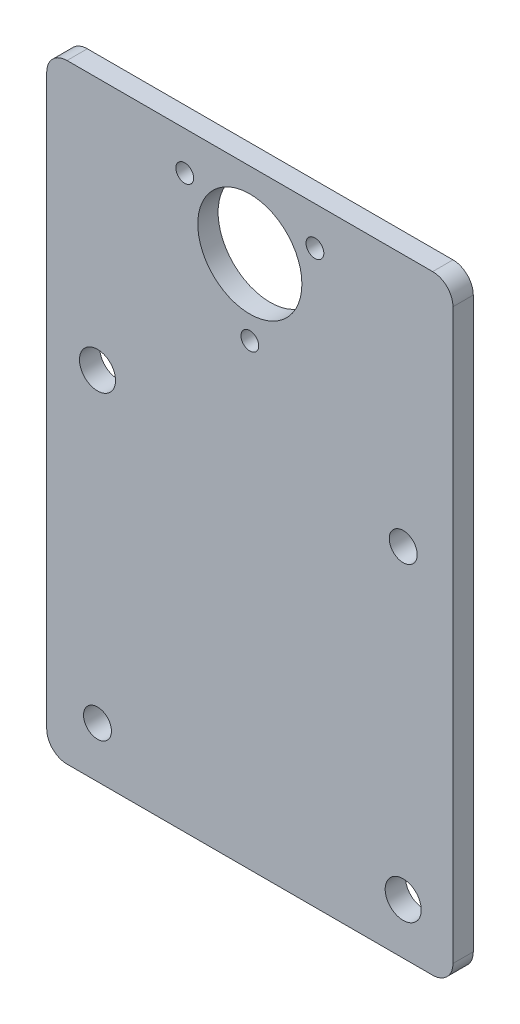
SolidWorks part; units mm, degrees
ref_plane "Płaszczyzna przednia" through (0, 0, 0) normal (0, 0, 1) x (1, 0, 0)
ref_plane "Płaszczyzna górna" through (0, 0, 0) normal (0, 1, 0) x (1, 0, 0)
ref_plane "Płaszczyzna prawa" through (0, 0, 0) normal (1, 0, 0) x (0, 0, -1)
sketch "Szkic1" plane through (0, 0, 0) normal (0, 0, 1) x (1, 0, 0)
  line L1 (-37.347, -20.7576) -> (42.653, -20.7576)
  line L2 (-37.347, -20.7576) -> (-37.347, 99.2424)
  line L3 (-37.347, 99.2424) -> (42.653, 99.2424)
  line L4 (42.653, -20.7576) -> (42.653, 99.2424)
  circle A0 centre (-27.347, 49.4424) radius 3.55
  circle A1 centre (-27.347, -10.7576) radius 2.75
  circle A2 centre (32.853, -10.7576) radius 3.55
  circle A3 centre (32.853, 49.4424) radius 2.75
  circle A4 centre (2.653, 84.2424) radius 10.25
  circle A5 centre (-10.1642, 91.6424) radius 1.75
  circle A6 centre (15.4702, 91.6424) radius 1.75
  circle A7 centre (2.653, 69.4424) radius 1.75
  point P21 (0, 0)
  point P24 (0, 0)
  dimension "D1" = 60.2
  dimension "D2" = 60.2
  dimension "D11" = 5.5
  dimension "D12" = 5.5
  dimension "D13" = 7.1
  dimension "D14" = 7.1
  dimension "D15" = 3.5
  dimension "D16" = 3.5
  dimension "D17" = 20.5
  dimension "3,5" = 3.5
  dimension "D18" = 14.8
  dimension "D19" = 14.8
  dimension "D20" = 14.8
  dimension "D3" = 60.2
  dimension "D4" = 60.2
  dimension "D5" = 10
  dimension "D6" = 10
  dimension "D7" = 10
  dimension "D8" = 10
  dimension "D9" = 80
  dimension "D10" = 120
  dimension "D23" = 40
  dimension "D24" = 15
extrude "Dodanie-wyciągnięcie1" add sketch "Szkic1" along normal blind 4
fillet "Zaokrąglenie1" radius 4 4 edges at (42.653, 99.2424, 2) (42.653, -20.7576, 2) (-37.347, -20.7576, 2) (-37.347, 99.2424, 2)
